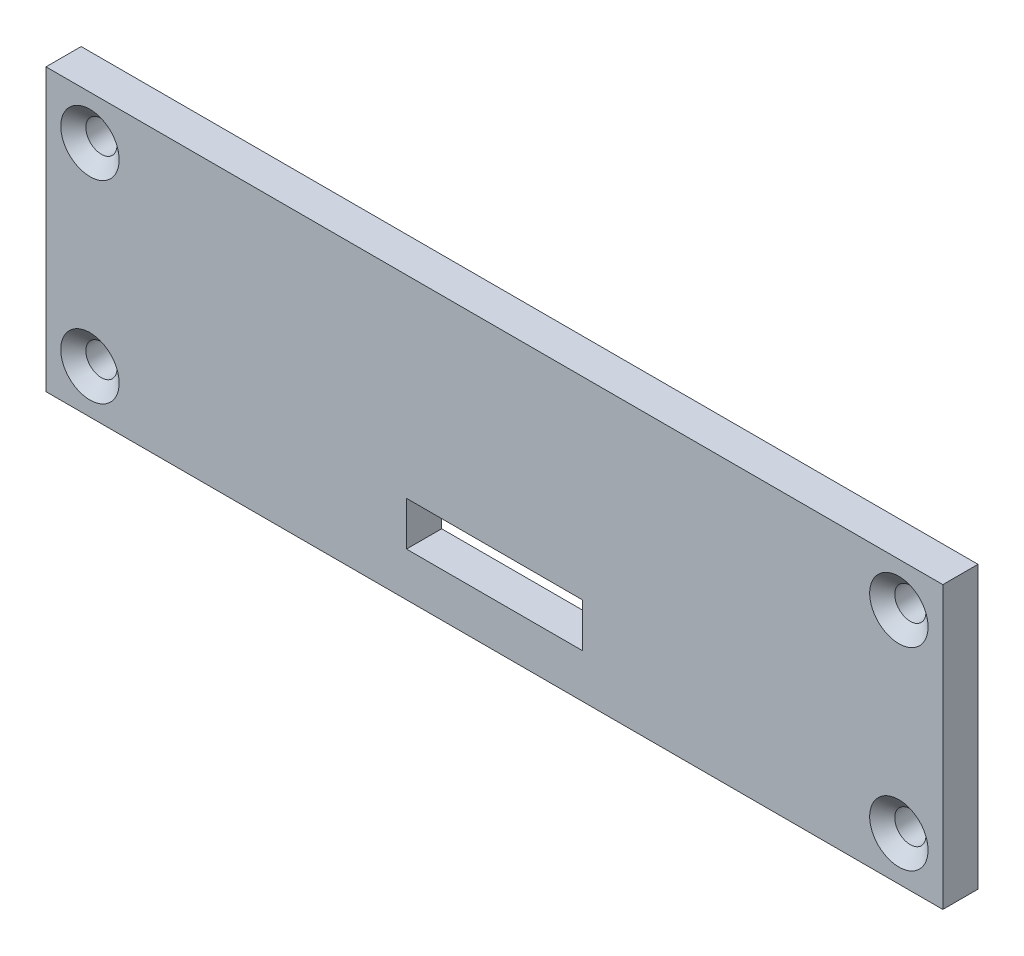
SolidWorks part; units mm, degrees
ref_plane "Front Plane" through (0, 0, 0) normal (0, 0, 1) x (1, 0, 0)
ref_plane "Top Plane" through (0, 0, 0) normal (0, 1, 0) x (1, 0, 0)
ref_plane "Right Plane" through (0, 0, 0) normal (1, 0, 0) x (0, 0, -1)
sketch "Sketch1" plane through (0, 0, 0) normal (0, 0, 1) x (1, 0, 0)
  line L1 (-64.77, -20.32) -> (64.77, -20.32)
  line L2 (-64.77, -20.32) -> (-64.77, 20.32)
  line L3 (-64.77, 20.32) -> (64.77, 20.32)
  line L4 (64.77, -20.32) -> (64.77, 20.32)
  line L5 (0, 20.32) -> (0, -20.32) construction
  line L6 (-64.77, 0) -> (64.77, 0) construction
  point P0 (0, 0)
  dimension "D1" = 129.54
  dimension "D2" = 40.64
extrude "Boss-Extrude1" add sketch "Sketch1" along normal blind 5.08
hole_wizard "CSK for #8 Flat Head Machine Screw (100)1" positions "Sketch4" profile "Sketch3" countersink size "#8" standard "ANSI Inch" end condition through all
sketch "Sketch4" plane through (0, 0, 5.08) normal (0, 0, 1) x (1, 0, 0)
  line L0 (64.77, 20.32) -> (-64.77, 20.32) construction
  line L1 (-64.77, 20.32) -> (-64.77, -20.32) construction
  line L2 (-64.77, -20.32) -> (64.77, -20.32) construction
  line L3 (64.77, -20.32) -> (64.77, 20.32) construction
  point P0 (-58.42, 13.97)
  point P2 (-58.42, -13.97)
  point P4 (58.42, -13.97)
  point P6 (58.42, 13.97)
  point P17 (0, 0)
  point P18 (0, 0)
  point P19 (0, 0)
  point P20 (0, 0)
  dimension "D1" = 6.35
  dimension "D2" = 6.35
  dimension "D3" = 6.35
  dimension "D4" = 6.35
sketch "Sketch3" plane through (-58.42, 13.97, 5.08) normal (1, 0, 0) x (0, -1, 0)
  line L0 (0, 0) -> (0, 5.08)
  line L1 (0, 5.08) -> (2.2479, 5.08)
  line L2 (2.2479, 5.08) -> (2.2479, 1.6518)
  line L3 (2.2479, 1.6518) -> (4.2164, 0)
  line L5 (4.2164, 0) -> (0, 0)
  line L6 (-2.2479, 1.6518) -> (-4.2164, 0) construction
  line L11 (0, -6.35) -> (0, 107.95) construction
  dimension "Thru Hole Dia." = 4.4958
  dimension "Thru Hole Depth" = 5.08
  dimension "Near C'Sink Dia." = 8.4328
  dimension "Near C'Sink Angle" = 100
sketch "Sketch5" plane through (0, 0, 5.08) normal (0, 0, 1) x (1, 0, 0)
  line L0 (-64.77, -20.32) -> (64.77, -20.32) construction
  line L1 (-12.7, -13.97) -> (12.7, -13.97)
  line L2 (-12.7, -13.97) -> (-12.7, -7.62)
  line L3 (-12.7, -7.62) -> (12.7, -7.62)
  line L4 (12.7, -13.97) -> (12.7, -7.62)
  line L5 (0, -7.62) -> (0, -13.97) construction
  line L6 (-12.7, -10.795) -> (12.7, -10.795) construction
  point P0 (0, -10.795)
  point P6 (0, 0)
  dimension "D1" = 6.35
  dimension "D2" = 25.4
  dimension "D3" = 6.35
extrude "Cut-Extrude1" cut sketch "Sketch5" against normal through all
